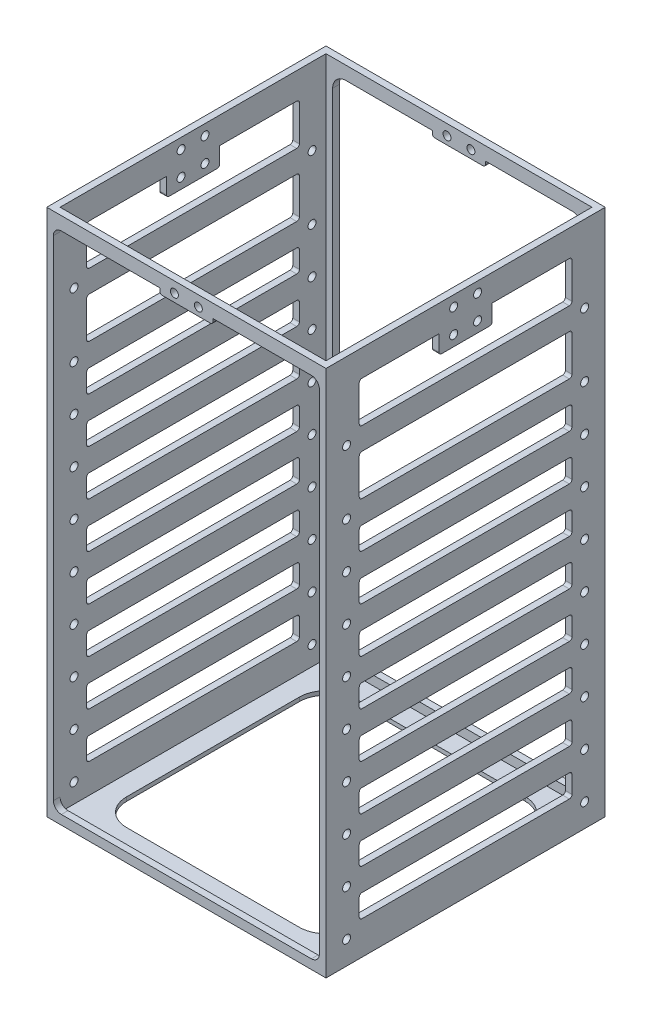
SolidWorks part; units mm, degrees
ref_plane "Front Plane" through (0, 0, 0) normal (0, 0, 1) x (1, 0, 0)
ref_plane "Top Plane" through (0, 0, 0) normal (0, 1, 0) x (1, 0, 0)
ref_plane "Right Plane" through (0, 0, 0) normal (1, 0, 0) x (0, 0, -1)
sketch "Sketch1" plane through (0, 0, 0) normal (0, 1, 0) x (1, 0, 0)
  line L1 (-52.5, -52.5) -> (52.5, -52.5)
  line L2 (-52.5, -52.5) -> (-52.5, 52.5)
  line L3 (-52.5, 52.5) -> (52.5, 52.5)
  line L4 (52.5, -52.5) -> (52.5, 52.5)
  line L5 (-52.5, -52.5) -> (52.5, 52.5) construction
  line L6 (-52.5, 52.5) -> (52.5, -52.5) construction
  line L7 (-32.5, -42.5) -> (32.5, -42.5)
  line L8 (-42.5, -32.5) -> (-42.5, 32.5)
  line L9 (-32.5, 42.5) -> (32.5, 42.5)
  line L10 (42.5, -32.5) -> (42.5, 32.5)
  line L11 (-42.5, -42.5) -> (42.5, 42.5) construction
  line L12 (-42.5, 42.5) -> (42.5, -42.5) construction
  arc A0 (32.5, -42.5) -> (42.5, -32.5) centre (32.5, -32.5) ccw
  arc A1 (32.5, 42.5) -> (42.5, 32.5) centre (32.5, 32.5) cw
  arc A2 (-42.5, 32.5) -> (-32.5, 42.5) centre (-32.5, 32.5) cw
  arc A3 (-32.5, -42.5) -> (-42.5, -32.5) centre (-32.5, -32.5) cw
  point P0 (0, 0)
  point P6 (0, 0)
  dimension "D3" = 10
  dimension "D1" = 105
  dimension "D2" = 42.5
extrude "Boss-Extrude2" add sketch "Sketch1" along normal blind 1.5 contours A3 L7 A0 L10 A1 L9 A2 L8 | L2 L1 L4 L3 region at (0, 0, 0)
sketch "Sketch3" plane through (0, 1.5, 0) normal (0, 1, 0) x (1, 0, 0)
  line L1 (-52.5, -52.5) -> (52.5, -52.5)
  line L2 (-52.5, -52.5) -> (-52.5, 52.5)
  line L3 (-52.5, 52.5) -> (52.5, 52.5)
  line L4 (52.5, -52.5) -> (52.5, 52.5)
  line L5 (-52.5, -52.5) -> (52.5, 52.5) construction
  line L6 (-52.5, 52.5) -> (52.5, -52.5) construction
  line L7 (-50, -50) -> (50, -50)
  line L8 (-50, -50) -> (-50, 50)
  line L9 (-50, 50) -> (50, 50)
  line L10 (50, -50) -> (50, 50)
  line L11 (-50, -50) -> (50, 50) construction
  line L12 (-50, 50) -> (50, -50) construction
  point P0 (0, 0)
  point P7 (0, 0)
  dimension "D1" = 2.5
extrude "Boss-Extrude3" add sketch "Sketch3" along normal blind 197 contours L8 L7 L10 L9 | L2 L3 L4 L1
sketch "Sketch4" plane through (0, 0, -52.5) normal (0, 0, 1) x (1, 0, 0)
  line L0 (-52.5, 0) -> (52.5, 0) construction
  line L1 (-42.5, 5) -> (42.5, 5)
  line L2 (-47.5, 10) -> (-47.5, 188.5)
  line L3 (-42.5, 193.5) -> (42.5, 193.5)
  line L4 (47.5, 10) -> (47.5, 188.5)
  line L5 (-47.5, 5) -> (47.5, 193.5) construction
  line L6 (-47.5, 193.5) -> (47.5, 5) construction
  line L7 (52.5, 198.5) -> (52.5, 0) construction
  line L8 (-50, 198.5) -> (50, 198.5) construction
  line L9 (-52.5, 198.5) -> (-52.5, 0) construction
  arc A0 (-42.5, 5) -> (-47.5, 10) centre (-42.5, 10) cw
  arc A1 (42.5, 5) -> (47.5, 10) centre (42.5, 10) ccw
  arc A2 (42.5, 193.5) -> (47.5, 188.5) centre (42.5, 188.5) cw
  arc A3 (-47.5, 188.5) -> (-42.5, 193.5) centre (-42.5, 188.5) cw
  point P0 (0, 99.25)
  dimension "D5" = 5
  dimension "D1" = 5
  dimension "D2" = 5
  dimension "D3" = 5
  dimension "D4" = 5
extrude "Cut-Extrude1" cut sketch "Sketch4" along normal up to surface (2.5 mm away) up to face at (0, 100, -50)
sketch "Sketch5" plane through (0, 0, 52.5) normal (0, 0, 1) x (1, 0, 0)
  line L0 (-52.5, 198.5) -> (52.5, 198.5) construction
  line L1 (-47, 3.5) -> (47, 3.5)
  line L2 (-50, 6.5) -> (-50, 190.5)
  line L3 (-47, 193.5) -> (47, 193.5)
  line L4 (50, 6.5) -> (50, 190.5)
  line L5 (-50, 3.5) -> (50, 193.5) construction
  line L6 (-50, 193.5) -> (50, 3.5) construction
  line L7 (-52.5, 1.5) -> (52.5, 1.5) construction
  line L8 (-52.5, 198.5) -> (-52.5, 0) construction
  line L9 (52.5, 198.5) -> (52.5, 0) construction
  arc A0 (47, 3.5) -> (50, 6.5) centre (47, 6.5) ccw
  arc A1 (-47, 3.5) -> (-50, 6.5) centre (-47, 6.5) cw
  arc A2 (47, 193.5) -> (50, 190.5) centre (47, 190.5) cw
  arc A3 (-50, 190.5) -> (-47, 193.5) centre (-47, 190.5) cw
  point P0 (0, 98.5)
  point P5 (0, 0)
  dimension "D5" = 3
  dimension "D1" = 5
  dimension "D2" = 2
  dimension "D3" = 2.5
  dimension "D4" = 2.5
sketch "Sketch6" plane through (52.5, 0, 0) normal (1, 0, 0) x (0, 0, -1)
  line L0 (-52.5, 3.5) -> (-52.5, 193.5) construction
  line L1 (52.5, 198.5) -> (52.5, 0) construction
  line L2 (-52.5, 0) -> (52.5, 0) construction
  circle A0 centre (-44.75, 8.75) radius 1.5
  circle A1 centre (44.75, 8.75) radius 1.5
  circle A2 centre (-44.75, 25.85) radius 1.5
  circle A3 centre (44.75, 25.85) radius 1.5
  circle A4 centre (-44.75, 42.95) radius 1.5
  circle A5 centre (44.75, 42.95) radius 1.5
  circle A6 centre (-44.75, 60.05) radius 1.5
  circle A7 centre (44.75, 60.05) radius 1.5
  circle A8 centre (-44.75, 77.15) radius 1.5
  circle A9 centre (44.75, 77.15) radius 1.5
  circle A10 centre (-44.75, 94.25) radius 1.5
  circle A11 centre (44.75, 94.25) radius 1.5
  circle A12 centre (-44.75, 111.35) radius 1.5
  circle A13 centre (44.75, 111.35) radius 1.5
  circle A14 centre (-44.75, 128.45) radius 1.5
  circle A15 centre (44.75, 128.45) radius 1.5
  circle A16 centre (-44.75, 145.55) radius 1.5
  circle A17 centre (44.75, 145.55) radius 1.5
  circle A18 centre (-44.75, 169.55) radius 1.5
  circle A19 centre (44.75, 169.55) radius 1.5
  dimension "D4" = 3
  dimension "D5" = 3
  dimension "D1" = 7.75
  dimension "D2" = 7.75
  dimension "D3" = 8.75
  dimension "D7" = 17.1
  dimension "D9" = 24
  dimension "D6" = 9
  dimension "D8" = 2
extrude "Cut-Extrude2" cut sketch "Sketch6" against normal through all
extrude "Cut-Extrude3" cut sketch "Sketch5" against normal up to surface (2.5 mm away) up to face at (0, 100, 50)
sketch "Sketch7" plane through (52.5, 0, 0) normal (1, 0, 0) x (0, 0, -1)
  line L0 (-40, 30.65) -> (-40, 37.15)
  line L1 (-39, 12.55) -> (39, 12.55)
  line L2 (-40, 13.55) -> (-40, 20.05)
  line L3 (-39, 21.05) -> (39, 21.05)
  line L4 (40, 13.55) -> (40, 20.05)
  line L5 (-40, 12.55) -> (40, 21.05) construction
  line L6 (-40, 21.05) -> (40, 12.55) construction
  line L7 (52.5, 198.5) -> (52.5, 0) construction
  line L8 (-39, 29.65) -> (39, 29.65)
  line L9 (40, 30.65) -> (40, 37.15)
  line L10 (-39, 38.15) -> (39, 38.15)
  line L11 (-40, 47.75) -> (-40, 54.25)
  line L12 (-39, 46.75) -> (39, 46.75)
  line L13 (40, 47.75) -> (40, 54.25)
  line L14 (-39, 55.25) -> (39, 55.25)
  line L15 (-40, 64.85) -> (-40, 71.35)
  line L16 (-39, 63.85) -> (39, 63.85)
  line L17 (40, 64.85) -> (40, 71.35)
  line L18 (-39, 72.35) -> (39, 72.35)
  line L19 (-40, 81.95) -> (-40, 88.45)
  line L20 (-39, 80.95) -> (39, 80.95)
  line L21 (40, 81.95) -> (40, 88.45)
  line L22 (-39, 89.45) -> (39, 89.45)
  line L23 (-40, 99.05) -> (-40, 105.55)
  line L24 (-39, 98.05) -> (39, 98.05)
  line L25 (40, 99.05) -> (40, 105.55)
  line L26 (-39, 106.55) -> (39, 106.55)
  line L27 (-40, 116.15) -> (-40, 122.65)
  line L28 (-39, 115.15) -> (39, 115.15)
  line L29 (40, 116.15) -> (40, 122.65)
  line L30 (-39, 123.65) -> (39, 123.65)
  line L31 (-40, 133.25) -> (-40, 139.75)
  line L32 (-39, 132.25) -> (39, 132.25)
  line L33 (40, 133.25) -> (40, 139.75)
  line L34 (-39, 140.75) -> (39, 140.75)
  circle A0 centre (-44.75, 8.75) radius 1.5 construction
  arc A1 (39, 21.05) -> (40, 20.05) centre (39, 20.05) cw
  arc A2 (39, 12.55) -> (40, 13.55) centre (39, 13.55) ccw
  arc A3 (-39, 12.55) -> (-40, 13.55) centre (-39, 13.55) cw
  arc A4 (-40, 20.05) -> (-39, 21.05) centre (-39, 20.05) cw
  arc A5 (-40, 37.15) -> (-39, 38.15) centre (-39, 37.15) cw
  arc A6 (-39, 29.65) -> (-40, 30.65) centre (-39, 30.65) cw
  arc A7 (39, 29.65) -> (40, 30.65) centre (39, 30.65) ccw
  arc A8 (39, 38.15) -> (40, 37.15) centre (39, 37.15) cw
  arc A9 (-40, 54.25) -> (-39, 55.25) centre (-39, 54.25) cw
  arc A10 (-39, 46.75) -> (-40, 47.75) centre (-39, 47.75) cw
  arc A11 (39, 46.75) -> (40, 47.75) centre (39, 47.75) ccw
  arc A12 (39, 55.25) -> (40, 54.25) centre (39, 54.25) cw
  arc A13 (-40, 71.35) -> (-39, 72.35) centre (-39, 71.35) cw
  arc A14 (-39, 63.85) -> (-40, 64.85) centre (-39, 64.85) cw
  arc A15 (39, 63.85) -> (40, 64.85) centre (39, 64.85) ccw
  arc A16 (39, 72.35) -> (40, 71.35) centre (39, 71.35) cw
  arc A17 (-40, 88.45) -> (-39, 89.45) centre (-39, 88.45) cw
  arc A18 (-39, 80.95) -> (-40, 81.95) centre (-39, 81.95) cw
  arc A19 (39, 80.95) -> (40, 81.95) centre (39, 81.95) ccw
  arc A20 (39, 89.45) -> (40, 88.45) centre (39, 88.45) cw
  arc A21 (-40, 105.55) -> (-39, 106.55) centre (-39, 105.55) cw
  arc A22 (-39, 98.05) -> (-40, 99.05) centre (-39, 99.05) cw
  arc A23 (39, 98.05) -> (40, 99.05) centre (39, 99.05) ccw
  arc A24 (39, 106.55) -> (40, 105.55) centre (39, 105.55) cw
  arc A25 (-40, 122.65) -> (-39, 123.65) centre (-39, 122.65) cw
  arc A26 (-39, 115.15) -> (-40, 116.15) centre (-39, 116.15) cw
  arc A27 (39, 115.15) -> (40, 116.15) centre (39, 116.15) ccw
  arc A28 (39, 123.65) -> (40, 122.65) centre (39, 122.65) cw
  arc A29 (-40, 139.75) -> (-39, 140.75) centre (-39, 139.75) cw
  arc A30 (-39, 132.25) -> (-40, 133.25) centre (-39, 133.25) cw
  arc A31 (39, 132.25) -> (40, 133.25) centre (39, 133.25) ccw
  arc A32 (39, 140.75) -> (40, 139.75) centre (39, 139.75) cw
  point P0 (0, 16.8)
  dimension "D5" = 1
  dimension "D1" = 8.5
  dimension "D2" = 3.8
  dimension "D3" = 80
  dimension "D4" = 12.5
  dimension "D7" = 8.6
  dimension "D6" = 8
extrude "Cut-Extrude4" cut sketch "Sketch7" against normal through all
sketch "Sketch8" plane through (52.5, 0, 0) normal (1, 0, 0) x (0, 0, -1)
  line L1 (-39, 149.35) -> (39, 149.35)
  line L2 (-40, 150.35) -> (-40, 163.75)
  line L3 (-39, 164.75) -> (39, 164.75)
  line L4 (40, 150.35) -> (40, 163.75)
  line L5 (-40, 149.35) -> (40, 164.75) construction
  line L6 (-40, 164.75) -> (40, 149.35) construction
  line L7 (52.5, 198.5) -> (52.5, 0) construction
  line L8 (-40, 188.55) -> (40, 173.15) construction
  line L9 (-40, 174.15) -> (-40, 187.55)
  line L10 (-39, 173.15) -> (39, 173.15)
  line L11 (40, 174.15) -> (40, 187.55)
  line L12 (-39, 188.55) -> (39, 188.55)
  circle A0 centre (-44.75, 145.55) radius 1.5 construction
  arc A2 (-40, 163.75) -> (-39, 164.75) centre (-39, 163.75) cw
  arc A3 (39, 164.75) -> (40, 163.75) centre (39, 163.75) cw
  arc A4 (39, 149.35) -> (40, 150.35) centre (39, 150.35) ccw
  arc A5 (-39, 149.35) -> (-40, 150.35) centre (-39, 150.35) cw
  arc A6 (-39, 173.15) -> (-40, 174.15) centre (-39, 174.15) cw
  arc A7 (-40, 187.55) -> (-39, 188.55) centre (-39, 187.55) cw
  arc A8 (39, 173.15) -> (40, 174.15) centre (39, 174.15) ccw
  arc A9 (39, 188.55) -> (40, 187.55) centre (39, 187.55) cw
  point P0 (0, 157.05)
  dimension "D5" = 1
  dimension "D1" = 3.8
  dimension "D2" = 15.4
  dimension "D3" = 80
  dimension "D4" = 12.5
  dimension "D7" = 8.4
  dimension "D6" = 2
extrude "Cut-Extrude5" cut sketch "Sketch8" against normal through all
sketch "Sketch15" plane through (52.5, 0, 0) normal (1, 0, 0) x (0, 0, -1)
  line L0 (39, 188.55) -> (-39, 188.55) construction
  line L1 (-10, 188.55) -> (10, 188.55)
  line L2 (-10, 188.55) -> (-10, 182.55)
  line L3 (-9, 181.55) -> (9, 181.55)
  line L4 (10, 188.55) -> (10, 182.55)
  line L5 (-52.5, 198.5) -> (-52.5, 0) construction
  arc A0 (9, 181.55) -> (10, 182.55) centre (9, 182.55) ccw
  arc A1 (-10, 182.55) -> (-9, 181.55) centre (-9, 182.55) ccw
  dimension "D4" = 1
  dimension "D1" = 20
  dimension "D2" = 7
  dimension "D3" = 42.5
extrude "Boss-Extrude4" add sketch "Sketch15" against normal up to surface (2.5 mm away) up to face at (50, 157.05, 0)
sketch "Sketch16" plane through (-52.5, 0, 0) normal (-1, 0, 0) x (0, 0, 1)
  line L1 (-10, 188.55) -> (10, 188.55)
  line L2 (-10, 188.55) -> (-10, 182.55)
  line L3 (-9, 181.55) -> (9, 181.55)
  line L4 (10, 188.55) -> (10, 182.55)
  arc A0 (9, 181.55) -> (10, 182.55) centre (9, 182.55) ccw
  arc A1 (-10, 182.55) -> (-9, 181.55) centre (-9, 182.55) ccw
  dimension "D3" = 1
  dimension "D1" = 7
  dimension "D2" = 20
extrude "Boss-Extrude5" add sketch "Sketch16" against normal up to surface (2.5 mm away) up to face at (-50, 157.05, 0)
sketch "Sketch9" plane through (52.5, 0, 0) normal (1, 0, 0) x (0, 0, -1)
  line L0 (-52.5, 198.5) -> (52.5, 198.5) construction
  line L1 (-52.5, 198.5) -> (-52.5, 0) construction
  line L2 (-10.0428, 190) -> (10.2919, 190) construction
  circle A0 centre (-4.5, 194.5) radius 1.5
  circle A1 centre (4.5, 194.5) radius 1.5
  circle A2 centre (4.5, 185.5) radius 1.5
  circle A3 centre (-4.5, 185.5) radius 1.5
  dimension "D1" = 3
  dimension "D3" = 9
  dimension "D5" = 3
  dimension "D2" = 4
  dimension "D4" = 48
  dimension "D6" = 4.5
extrude "Cut-Extrude6" cut sketch "Sketch9" against normal through all
sketch "Sketch17" plane through (0, 0, 52.5) normal (0, 0, 1) x (1, 0, 0)
  line L0 (47, 193.5) -> (-47, 193.5) construction
  line L1 (-10, 193.5) -> (10, 193.5)
  line L2 (-10, 193.5) -> (-10, 192.5)
  line L3 (-9, 191.5) -> (9, 191.5)
  line L4 (10, 193.5) -> (10, 192.5)
  line L5 (-52.5, 198.5) -> (-52.5, 0) construction
  arc A0 (9, 191.5) -> (10, 192.5) centre (9, 192.5) ccw
  arc A1 (-10, 192.5) -> (-9, 191.5) centre (-9, 192.5) ccw
  dimension "D4" = 1
  dimension "D1" = 20
  dimension "D2" = 42.5
  dimension "D3" = 2
extrude "Boss-Extrude6" add sketch "Sketch17" against normal up to surface (2.5 mm away) up to face at (0, 194.3738, 50)
sketch "Sketch18" plane through (0, 0, -52.5) normal (0, 0, -1) x (-1, 0, 0)
  line L1 (-10, 193.5) -> (10, 193.5)
  line L2 (-10, 193.5) -> (-10, 192.5)
  line L3 (-9, 191.5) -> (9, 191.5)
  line L4 (10, 193.5) -> (10, 192.5)
  arc A0 (9, 191.5) -> (10, 192.5) centre (9, 192.5) ccw
  arc A1 (-10, 192.5) -> (-9, 191.5) centre (-9, 192.5) ccw
  dimension "D3" = 1
  dimension "D1" = 2
  dimension "D2" = 20
extrude "Boss-Extrude7" add sketch "Sketch18" against normal up to surface (2.5 mm away) up to face at (0, 99.25, -50)
sketch "Sketch19" plane through (0, 0, 52.5) normal (0, 0, 1) x (1, 0, 0)
  line L0 (0, 198.5) -> (0, 191.5) construction
  line L1 (-9, 191.5) -> (9, 191.5) construction
  line L3 (-52.5, 198.5) -> (52.5, 198.5) construction
  circle A0 centre (-4.5, 194.5) radius 1.5
  circle A1 centre (4.5, 194.5) radius 1.5
  dimension "D1" = 3
  dimension "D2" = 4
  dimension "D3" = 4.5
extrude "Cut-Extrude7" cut sketch "Sketch19" against normal through all
